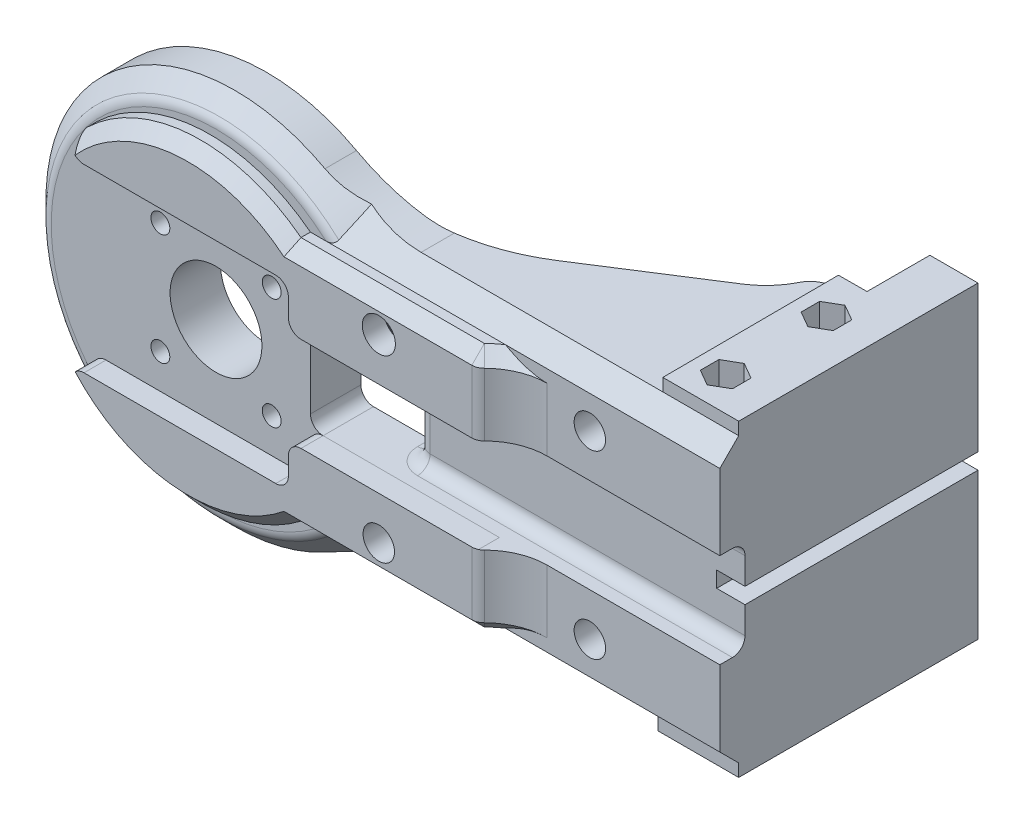
SolidWorks part; units mm, degrees
ref_plane "前视基准面" through (0, 0, 0) normal (0, 0, 1) x (1, 0, 0)
ref_plane "上视基准面" through (0, 0, 0) normal (0, 1, 0) x (1, 0, 0)
ref_plane "右视基准面" through (0, 0, 0) normal (1, 0, 0) x (0, 0, -1)
sketch "草图1" plane through (0, 0, 0) normal (0, 0, 1) x (1, 0, 0)
  line L0 (2.8101, 15.0444) -> (15.3101, 15.0444) construction
  line L1 (2.8101, 15.0444) -> (11.649, 23.8832) construction
  line L2 (2.8101, 15.0444) -> (-6.0287, 23.8832) construction
  circle A0 centre (2.8101, 15.0444) radius 30
  circle A1 centre (2.8101, 15.0444) radius 12.5 construction
  circle A2 centre (-6.0287, 23.8832) radius 1.5
  circle A3 centre (11.649, 23.8832) radius 1.5
  circle A4 centre (11.649, 6.2056) radius 1.5
  circle A5 centre (-6.0287, 6.2056) radius 1.5
  circle A6 centre (2.8101, 15.0444) radius 11.25 construction
  circle A7 centre (2.8101, 15.0444) radius 7.2938
  circle A8 centre (2.8101, 15.0444) radius 10 construction
  dimension "D1" = 25
  dimension "D2" = 60
  dimension "D3" = 22.5
extrude "凸台-拉伸1" add sketch "草图1" along normal blind 8
sketch "Sketch2" plane through (0, 0, 8) normal (0, 0, 1) x (1, 0, 0)
  line L0 (10.1039, 15.0444) -> (19.5752, 15.0444) construction
  line L1 (2.8101, 22.3382) -> (2.8101, 32.2947) construction
  line L2 (82.8101, 37.5444) -> (14.8101, 37.5444)
  line L3 (82.8101, 37.5444) -> (82.8101, -7.4556)
  line L4 (82.8101, -7.4556) -> (14.8101, -7.4556)
  line L5 (14.8101, 37.5444) -> (14.8101, -7.4556)
  line L6 (82.8101, 37.5444) -> (14.8101, -7.4556) construction
  line L7 (82.8101, -7.4556) -> (14.8101, 37.5444) construction
  point P1 (48.8101, 15.0444)
  dimension "D1" = 80
  dimension "D2" = 12
  dimension "D3" = 45
extrude "Boss-Extrude1" add sketch "Sketch2" against normal up to surface (8 mm away) up to face at (32.8101, 15.0444, 0)
sketch "Sketch3" plane through (0, 0, 0) normal (0, 0, -1) x (-1, 0, 0)
  line L0 (-82.8101, -7.4556) -> (-22.6533, -7.4556) construction
  line L1 (-82.8101, 37.5444) -> (-67.8101, 37.5444)
  line L2 (-82.8101, 37.5444) -> (-82.8101, -7.4556)
  line L3 (-82.8101, -7.4556) -> (-67.8101, -7.4556)
  line L4 (-67.8101, 37.5444) -> (-67.8101, -7.4556)
  dimension "D1" = 15
extrude "Boss-Extrude2" add sketch "Sketch3" along normal blind 34.5
sketch "Sketch4" plane through (0, 0, 8) normal (0, 0, 1) x (1, 0, 0)
  line L0 (1.3377, 15.0444) -> (12.0766, 15.0444) construction
  line L1 (2.8101, 22.3382) -> (2.8101, 29.0747) construction
  line L3 (17.8101, 22.5444) -> (30.8101, 22.5444)
  line L4 (17.8101, 22.5444) -> (17.8101, 7.5444)
  line L5 (17.8101, 7.5444) -> (30.8101, 7.5444)
  line L6 (30.8101, 22.5444) -> (30.8101, 7.5444)
  line L7 (17.8101, 22.5444) -> (30.8101, 7.5444) construction
  line L8 (17.8101, 7.5444) -> (30.8101, 22.5444) construction
  point P2 (24.3101, 15.0444)
  dimension "D1" = 15
  dimension "D2" = 13
  dimension "D3" = 15
extrude "Cut-Extrude1" cut sketch "Sketch4" against normal blind 38
sketch "Sketch5" plane through (0, 0, 8) normal (0, 0, 1) x (1, 0, 0)
  line L1 (30.8101, 22.5444) -> (86.2388, 22.5444)
  line L2 (30.8101, 22.5444) -> (30.8101, 7.5444)
  line L3 (30.8101, 7.5444) -> (86.2388, 7.5444)
  line L4 (86.2388, 22.5444) -> (86.2388, 7.5444)
extrude "Cut-Extrude2" cut sketch "Sketch5" against normal blind 4
sketch "Sketch6" plane through (0, 37.5444, 0) normal (0, 1, 0) x (1, 0, 0)
  line L0 (36.9807, 0) -> (67.8101, 19.715)
  line L1 (22.6533, 0) -> (67.8101, 0) construction
  line L2 (67.8101, 34.5) -> (67.8101, 0) construction
  line L3 (67.8101, 19.715) -> (67.8101, 0)
  line L4 (67.8101, 0) -> (36.9807, 0)
extrude "Boss-Extrude3" add sketch "Sketch6" against normal up to surface (45 mm away) up to face at (57.7578, -7.4556, -8.8333)
fillet "Fillet1" radius 30 1 edges at (36.9807, 15.0444, 0)
chamfer "Chamfer1" distance 3 angle 45 3 edges at (52.7317, -7.4556, 8) (52.7317, 37.5444, 8) (-27.1899, 15.0444, 8)
fillet "Fillet2" radius 2 8 edges at (17.8101, 22.5444, 4) (56.8101, 22.5444, 4) (30.8101, 22.5444, 1.9435) (56.8101, 7.5444, 4) (-24.1899, 15.0444, 8) (17.8101, 7.5444, 4) (30.8101, 7.5444, 1.9435) (30.8101, 15.0444, 4)
sketch "Sketch7" plane through (0, 0, 8) normal (0, 0, 1) x (1, 0, 0)
  line L0 (10.1039, 15.0444) -> (24.688, 15.0444) construction
  line L2 (32.1588, 29.3728) -> (62.173, 29.3728) construction
  line L3 (32.1588, 29.3728) -> (32.1588, 0.716) construction
  line L4 (32.1588, 0.716) -> (62.173, 0.716) construction
  line L5 (62.173, 29.3728) -> (62.173, 0.716) construction
  line L6 (32.1588, 29.3728) -> (62.173, 0.716) construction
  line L7 (32.1588, 0.716) -> (62.173, 29.3728) construction
  circle A0 centre (32.1588, 29.3728) radius 2.5
  circle A1 centre (62.173, 29.3728) radius 2.5
  circle A2 centre (32.1588, 0.716) radius 2.5
  circle A3 centre (62.173, 0.716) radius 2.5
  point P1 (47.1659, 15.0444)
extrude "Cut-Extrude3" cut sketch "Sketch7" against normal blind 16
sketch "Sketch8" plane through (0, 37.5444, 0) normal (0, 1, 0) x (1, 0, 0)
  line L0 (75.3101, 33) -> (75.3101, -24.1995) construction
  line L2 (75.3101, 3.3773) -> (72.7601, 1.905)
  line L3 (72.7601, 1.905) -> (72.7601, -1.0395)
  line L4 (72.7601, -1.0395) -> (75.3101, -2.5117)
  line L5 (75.3101, -2.5117) -> (77.8601, -1.0395)
  line L6 (77.8601, -1.0395) -> (77.8601, 1.905)
  line L7 (77.8601, 1.905) -> (75.3101, 3.3773)
  line L14 (75.3101, 19.3773) -> (72.7601, 17.905)
  line L15 (72.7601, 17.905) -> (72.7601, 14.9605)
  line L16 (72.7601, 14.9605) -> (75.3101, 13.4883)
  line L17 (75.3101, 13.4883) -> (77.8601, 14.9605)
  line L18 (77.8601, 14.9605) -> (77.8601, 17.905)
  line L19 (77.8601, 17.905) -> (75.3101, 19.3773)
  circle A3 centre (75.3101, 0.4328) radius 2.55 construction
  circle A4 centre (75.3101, 16.4328) radius 2.55 construction
  dimension "D1" = 5.1
  dimension "D2" = 5.1
  dimension "D3" = 16
extrude "Cut-Extrude4" cut sketch "Sketch8" against normal blind 56
fillet "Fillet3" radius 12 1 edges at (67.8101, 15.0444, -19.715)
mirror "Mirror1" about plane through (0, 0, -34.5) normal (0, 0, -1) of bodies 119
sketch "Sketch9" plane through (0, 37.5444, 0) normal (0, 1, 0) x (1, 0, 0)
  line L0 (67.8101, 33) -> (62.8933, 33) construction
  line L3 (44.1928, 43) -> (75.1685, 43)
  line L4 (44.1928, 43) -> (44.1928, 23)
  line L5 (44.1928, 23) -> (75.1685, 23)
  line L6 (75.1685, 43) -> (75.1685, 23)
  line L7 (44.1928, 43) -> (75.1685, 23) construction
  line L8 (44.1928, 23) -> (75.1685, 43) construction
  point P1 (59.6807, 33)
  dimension "D1" = 20
extrude "Cut-Extrude5" cut sketch "Sketch9" against normal blind 79
fillet "Fillet4" radius 3.8 4 edges at (75.1685, 15.0444, -23) (67.3517, 15.0444, -23) (75.1685, 15.0444, -43) (67.8067, 15.0444, -43)
sketch "Sketch10" plane through (0, 0, 4) normal (0, 0, 1) x (1, 0, 0)
  line L0 (82.4643, 15.0671) -> (92.2834, 15.0671) construction
  line L3 (93.2139, 16.3271) -> (78.3101, 16.3271)
  line L4 (93.2139, 16.3271) -> (93.2139, 13.8071)
  line L5 (93.2139, 13.8071) -> (78.3101, 13.8071)
  line L6 (78.3101, 16.3271) -> (78.3101, 13.8071)
  line L7 (93.2139, 16.3271) -> (78.3101, 13.8071) construction
  line L8 (93.2139, 13.8071) -> (78.3101, 16.3271) construction
  line L9 (82.8101, 20.5444) -> (82.8101, 9.5444) construction
  point P1 (85.762, 15.0671)
  dimension "D1" = 2.52
  dimension "D2" = 4.5
extrude "Cut-Extrude6" cut sketch "Sketch10" against normal blind 79
sketch "Sketch11" plane through (0, 0, 8) normal (0, 0, 1) x (1, 0, 0)
  line L0 (19.7803, -4.4556) -> (17.4125, -4.4556) construction
  line L1 (82.8101, 34.5444) -> (20.2658, 34.5444) construction
  line L2 (47.7999, 34.5444) -> (17.7999, 34.5444)
  line L3 (47.7999, 34.5444) -> (47.7999, -4.4556) construction
  line L4 (47.7999, -4.4556) -> (17.7999, -4.4556)
  line L5 (17.7999, 34.5444) -> (17.7999, -4.4556) construction
  line L6 (47.7999, 34.5444) -> (47.7999, 22.5444)
  line L7 (32.8101, 22.5444) -> (82.8101, 22.5444) construction
  line L8 (47.7999, 22.5444) -> (17.7999, 22.5444)
  line L9 (82.8101, 22.5444) -> (19.8101, 22.5444) construction
  line L10 (17.7999, 22.5444) -> (17.7999, 34.5444) construction
  line L11 (17.7999, -4.4556) -> (17.7999, 7.547) construction
  line L12 (17.7999, 7.547) -> (47.7999, 7.5444)
  line L13 (82.8101, 7.5444) -> (32.8101, 7.5444) construction
  line L14 (19.8101, 7.5444) -> (82.8101, 7.5444) construction
  line L15 (47.7999, 7.5444) -> (47.7999, -4.4556)
  line L16 (-19.0908, 29.3728) -> (17.7999, 29.3728)
  line L17 (-19.0908, 29.3728) -> (-19.0908, 0.716) construction
  line L18 (-19.0908, 0.716) -> (17.7999, 0.716)
  line L19 (17.7999, 0.716) -> (17.7999, 7.547)
  line L20 (17.7999, 22.5444) -> (17.7999, 29.3728)
  circle A0 centre (32.1588, 29.3728) radius 2.6301
  circle A1 centre (32.1588, 0.716) radius 2.5
  arc A2 (20.2658, 34.5444) -> (20.2658, -4.4556) centre (2.8101, 15.0444) ccw construction
  arc A3 (-19.0908, 29.3728) -> (17.7999, 34.5444) centre (1.8664, 14.0412) cw
  arc A4 (-19.0908, 0.716) -> (17.7999, -4.4556) centre (1.8922, 16.2323) ccw
  dimension "D1" = 30
extrude "Boss-Extrude4" add sketch "Sketch11" along normal blind 3.5
fillet "Fillet5" radius 10 5 edges at (47.7999, 28.5444, 8) (47.7999, 22.5444, 9.75) (47.7999, 34.5444, 9.75) (47.7999, 1.5444, 8) (47.7999, -4.4556, 9.75)
fillet "Fillet6" radius 2 2 edges at (47.7999, 28.5444, 11.5) (47.7999, 1.5444, 11.5)
chamfer "Chamfer2" distance 2 angle 45 6 edges at (51.5804, -4.4556, 8.7579) (47.6924, -4.4556, 11.3484) (32.3643, -4.4556, 11.5) (51.5804, 34.5444, 8.7579) (47.6924, 34.5444, 11.3484) (32.3643, 34.5444, 11.5)
sketch "Sketch12" plane through (0, 0, -77) normal (0, 0, -1) x (-1, 0, 0)
  line L0 (-20.2658, -4.4556) -> (-82.8101, -4.4556) construction
  line L1 (-20.2658, 34.5444) -> (-50.2658, 34.5444)
  line L2 (-20.2658, 34.5444) -> (-20.2658, -4.4556) construction
  line L3 (-20.2658, -4.4556) -> (-50.2658, -4.4556)
  line L4 (-50.2658, 34.5444) -> (-50.2658, -4.4556) construction
  line L5 (-20.2658, 34.5444) -> (-20.2658, 22.5444)
  line L6 (-82.8101, 22.5444) -> (-19.8101, 22.5444) construction
  line L7 (-20.2658, 22.5444) -> (-50.2658, 22.5444)
  line L8 (-50.2658, 22.5444) -> (-50.2658, 34.5444)
  line L9 (-50.2658, 7.5444) -> (-50.2658, -4.4556)
  line L10 (-19.8101, 7.5444) -> (-82.8101, 7.5444) construction
  line L11 (-82.8101, 7.5444) -> (-32.8101, 7.5444) construction
  line L14 (-20.2658, -4.4556) -> (-20.2658, 7.5444)
  line L15 (-20.2658, 7.5444) -> (-50.2658, 7.5444)
  circle A0 centre (-32.1588, 29.3728) radius 2.5
  circle A1 centre (-32.1588, 0.716) radius 2.5153
  dimension "D1" = 30
extrude "Boss-Extrude5" add sketch "Sketch12" along normal blind 3.5
fillet "Fillet7" radius 10 6 edges at (50.2658, 28.5444, -77) (50.2658, 34.5444, -78.75) (50.2658, 22.5444, -78.75) (50.2658, 1.5444, -77) (50.2658, 7.5444, -78.75) (50.2658, -4.4556, -78.75)
fillet "Fillet8" radius 2 6 edges at (20.038, 7.5444, -77) (20.038, 22.5444, -77) (50.2658, 28.5444, -80.5) (20.2658, 28.5444, -77) (50.2658, 1.5444, -80.5) (20.2658, 1.5444, -77)
chamfer "Chamfer3" distance 2 angle 45 6 edges at (54.0463, -4.4556, -77.7579) (50.1584, -4.4556, -80.3484) (34.8302, -4.4556, -80.5) (54.0463, 34.5444, -77.7579) (50.1584, 34.5444, -80.3484) (34.8302, 34.5444, -80.5)
sketch "Sketch13" plane through (0, 37.5444, 0) normal (0, 1, 0) x (1, 0, 0)
  line L0 (75.1685, 33) -> (-30.2804, 34.3505)
  line L1 (75.1685, 26.8) -> (75.1685, 39.2) construction
  line L2 (-30.2804, 34.3505) -> (-30.2804, 87.4319)
  line L3 (-30.2804, 87.4319) -> (87.5454, 92.3662)
  line L4 (87.5454, 92.3662) -> (91.433, 44.9668)
  line L5 (91.433, 44.9668) -> (82.8101, 33)
  line L6 (82.8101, 74) -> (82.8101, -5) construction
  line L7 (82.8101, 33) -> (75.1685, 33)
extrude "Cut-Extrude7" cut sketch "Sketch13" against normal through all both and the other way through all
fillet "Fillet9" radius 2 6 edges at (17.7999, 22.5444, 9.75) (17.7999, 7.547, 9.75) (17.7999, 0.716, 9.75) (17.7999, 29.3728, 9.75) (-19.0908, 0.716, 9.75) (-19.0908, 29.3728, 9.75)
chamfer "Chamfer4" distance 2 angle 45 2 edges at (2.096, -9.8637, 11.5) (2.0637, 40.0069, 11.5)
sketch "Sketch14" plane through (0, 37.5444, 0) normal (0, 1, 0) x (1, 0, 0)
  line L0 (70.7646, -5) -> (82.8101, -5)
  line L1 (22.6533, -5) -> (82.8101, -5) construction
  line L2 (82.8101, -5) -> (82.8101, 33)
  line L3 (82.8101, 33) -> (75.1685, 33)
  line L4 (75.1685, 33) -> (75.1685, 23.0184)
  line L5 (75.1685, 23.0184) -> (70.6505, 23)
  line L6 (69.9325, 23) -> (71.3685, 23) construction
  line L7 (70.6505, 23) -> (70.7646, -5)
  line L9 (77.8601, 17.905) -> (75.3101, 19.3773) construction
  line L10 (77.8601, 17.905) -> (75.3101, 19.3773)
  line L11 (72.7601, 1.905) -> (72.7601, -1.0395) construction
  line L12 (72.7601, -1.0395) -> (75.3101, -2.5117) construction
  line L13 (75.3101, -2.5117) -> (77.8601, -1.0395) construction
  line L14 (77.8601, -1.0395) -> (77.8601, 1.905) construction
  line L15 (77.8601, 1.905) -> (75.3101, 3.3773) construction
  line L16 (75.3101, 3.3773) -> (72.7601, 1.905) construction
  line L17 (77.8601, 14.9605) -> (77.8601, 17.905) construction
  line L18 (75.3101, 13.4883) -> (77.8601, 14.9605) construction
  line L19 (72.7601, 14.9605) -> (75.3101, 13.4883) construction
  line L20 (72.7601, 17.905) -> (72.7601, 14.9605) construction
  line L21 (75.3101, 19.3773) -> (72.7601, 17.905) construction
  line L22 (72.7601, 1.905) -> (72.7601, -1.0395)
  line L23 (72.7601, -1.0395) -> (75.3101, -2.5117)
  line L24 (75.3101, -2.5117) -> (77.8601, -1.0395)
  line L25 (77.8601, -1.0395) -> (77.8601, 1.905)
  line L26 (77.8601, 1.905) -> (75.3101, 3.3773)
  line L27 (75.3101, 3.3773) -> (72.7601, 1.905)
  line L28 (77.8601, 14.9605) -> (77.8601, 17.905)
  line L29 (75.3101, 13.4883) -> (77.8601, 14.9605)
  line L30 (72.7601, 14.9605) -> (75.3101, 13.4883)
  line L31 (72.7601, 17.905) -> (72.7601, 14.9605)
  line L32 (75.3101, 19.3773) -> (72.7601, 17.905)
  point P14 (0, 0)
extrude "Boss-Extrude6" add sketch "Sketch14" along normal blind 2
sketch "Sketch15" plane through (0, -7.4556, 0) normal (0, -1, 0) x (1, 0, 0)
  line L0 (75.1685, -33) -> (82.8101, -33)
  line L1 (82.8101, -33) -> (82.8101, 5)
  line L2 (82.8101, 5) -> (69.9828, 5)
  line L3 (82.8101, 5) -> (22.6533, 5) construction
  line L4 (69.9828, 5) -> (69.9828, -23)
  line L5 (71.3685, -23) -> (69.9325, -23) construction
  line L6 (69.9828, -23) -> (75.1685, -23)
  line L7 (75.1685, -23) -> (75.1685, -33)
  line L8 (75.3101, -13.4883) -> (72.7601, -14.9605) construction
  line L9 (77.8601, -14.9605) -> (75.3101, -13.4883) construction
  line L10 (75.3101, -13.4883) -> (72.7601, -14.9605)
  line L11 (77.8601, -14.9605) -> (75.3101, -13.4883)
  line L12 (72.7601, -14.9605) -> (72.7601, -17.905) construction
  line L13 (72.7601, -14.9605) -> (72.7601, -17.905)
  line L14 (75.3101, -3.3773) -> (77.8601, -1.905)
  line L15 (72.7601, -1.905) -> (75.3101, -3.3773)
  line L16 (72.7601, 1.0395) -> (72.7601, -1.905)
  line L17 (75.3101, 2.5117) -> (72.7601, 1.0395)
  line L18 (77.8601, 1.0395) -> (75.3101, 2.5117)
  line L19 (77.8601, -1.905) -> (77.8601, 1.0395)
  line L20 (75.3101, -3.3773) -> (77.8601, -1.905)
  line L21 (72.7601, -1.905) -> (75.3101, -3.3773)
  line L22 (72.7601, 1.0395) -> (72.7601, -1.905)
  line L23 (75.3101, 2.5117) -> (72.7601, 1.0395)
  line L24 (77.8601, 1.0395) -> (75.3101, 2.5117)
  line L25 (77.8601, -1.905) -> (77.8601, 1.0395)
  line L26 (77.8601, -17.905) -> (77.8601, -14.9605) construction
  line L27 (75.3101, -19.3773) -> (77.8601, -17.905) construction
  line L28 (72.7601, -17.905) -> (75.3101, -19.3773) construction
  line L29 (77.8601, -17.905) -> (77.8601, -14.9605)
  line L30 (75.3101, -19.3773) -> (77.8601, -17.905)
  line L31 (72.7601, -17.905) -> (75.3101, -19.3773)
  dimension "D1" = 0
extrude "Boss-Extrude7" add sketch "Sketch15" along normal blind 2
fillet "Fillet10" radius 32 2 edges at (22.6533, 37.5444, 2.5) (22.6533, -7.4556, 2.5)
